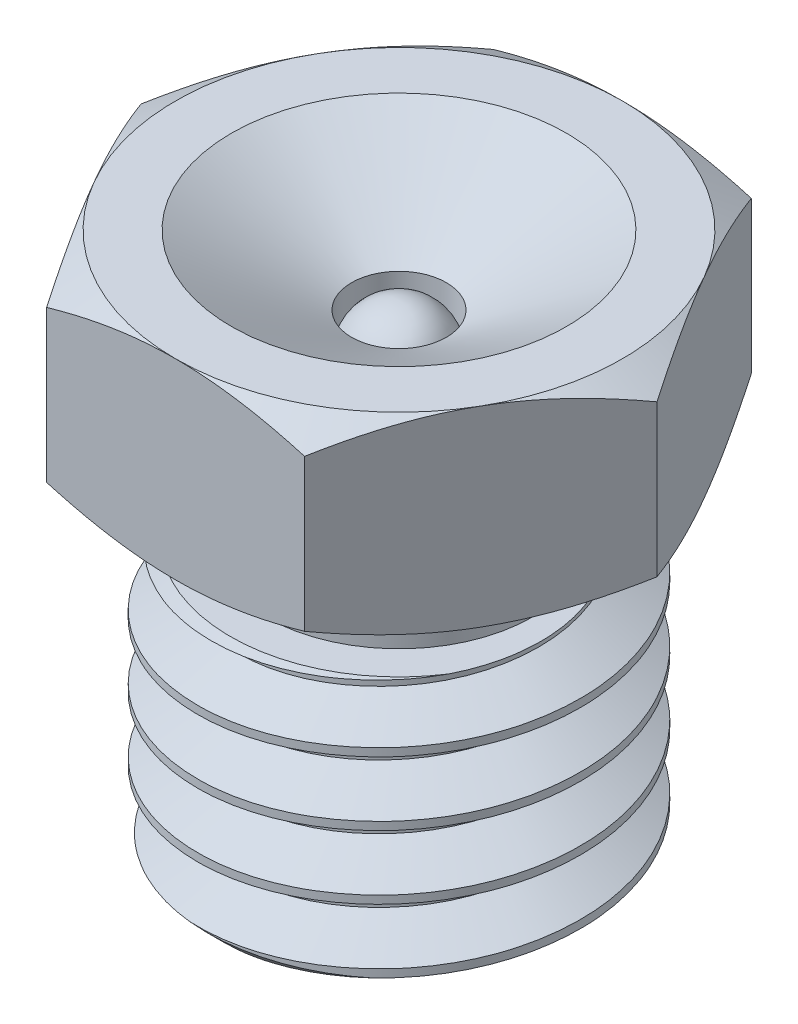
SolidWorks part; units mm, degrees
ref_plane "Front" through (0, 0, 0) normal (0, 0, 1) x (1, 0, 0)
ref_plane "Top" through (0, 0, 0) normal (0, 1, 0) x (1, 0, 0)
ref_plane "Right" through (0, 0, 0) normal (1, 0, 0) x (0, 0, -1)
sketch "Sketch1" plane through (0, 0, 0) normal (0, 0, 1) x (1, 0, 0)
  line L0 (0, 3) -> (0, -6) construction
  point P2 (0, -1.2)
  point P3 (0, 0)
  point P5 (0, -5.4)
  dimension "D1" = 0.6
sketch "Sketch2" plane through (0, 0, 0) normal (0, 0, 1) x (1, 0, 0)
  line L0 (0, 0) -> (0, -6)
  line L1 (0, 0) -> (2.1, 0)
  line L2 (2.1, 0) -> (2.1, -1.2)
  line L3 (2.1, -1.2) -> (3, -1.2)
  line L4 (3, -1.2) -> (3, -5.4)
  line L5 (3, -5.4) -> (1.65, -5.4)
  line L6 (1.65, -5.4) -> (1.65, -6)
  line L7 (1.65, -6) -> (0, -6)
  point P10 (-1.65, -6)
  point P11 (-3, -1.2)
  point P14 (-2.1, 0)
  point P15 (-3, -5.4)
  point P16 (3, -4.4)
  point P17 (-3, -4.4)
  dimension "D3" = 3.3
  dimension "D1" = 6
  dimension "D2" = 0.6
  dimension "D4" = 1
  dimension "D5" = 4.2
revolve "Revolve1" add sketch "Sketch2" angle 360 mid plane about L0
sketch "Sketch3" plane through (0, -5.4, 0) normal (0, -1, 0) x (1, 0, 0)
  circle A0 centre (0, 0) radius 3
chamfer "Chamfer1" distance 0.36 angle 45 2 edges at (-3, -5.4, 0) (-3, -1.2, 0)
curve "Helix/Spiral1" pitch 1 height 5.2 radius 3 centre (0, -5.4, 0) axis (0, 1, 0) start towards (1, 0, 0)
fillet "Fillet1" radius 0.231 2 edges at (-1.65, -6, 0) (-1.65, -5.4, 0)
sketch "Sketch4" plane through (0, 0, 0) normal (0, 0, 1) x (1, 0, 0)
  line L0 (-3, -5.4) -> (-3, -6.275)
  line L1 (-3, -5.4) -> (-2.3505, -5.775)
  line L2 (-2.3505, -5.775) -> (-2.3505, -5.9)
  line L3 (-2.3505, -5.9) -> (-3, -6.275)
  line L6 (-2.6752, -5.5875) -> (-2.6752, -6.0875) construction
  dimension "D1" = 60
  dimension "D3" = 0.125
  dimension "D4" = 0.5
sweep "Cut-Sweep1" cut profiles "Sketch4" path "Helix/Spiral1" align with end faces yes
sketch "Sketch5" plane through (0, 0, 0) normal (0, 1, 0) x (1, 0, 0)
  line L1 (4.0415, 0) -> (2.0207, 3.5)
  line L2 (2.0207, 3.5) -> (-2.0207, 3.5)
  line L3 (-2.0207, 3.5) -> (-4.0415, 0)
  line L4 (-4.0415, 0) -> (-2.0207, -3.5)
  line L5 (-2.0207, -3.5) -> (2.0207, -3.5)
  line L6 (2.0207, -3.5) -> (4.0415, 0)
  circle A0 centre (0, 0) radius 3.5 construction
extrude "Boss-Extrude1" add sketch "Sketch5" along normal up to vertex (3 mm away) up to point (0, 3, 0)
sketch "Sketch6" plane through (0, 0, 0) normal (0, -1, 0) x (1, 0, 0)
  line L0 (-4.0415, 0) -> (-2.0207, 3.5) construction
  circle A0 centre (0, 0) radius 3.5
extrude "Cut-Extrude1" cut sketch "Sketch6" against normal blind 2.54 draft 60 flip side to cut
sketch "Sketch7" plane through (0, 3, 0) normal (0, 1, 0) x (1, 0, 0)
  circle A0 centre (0, 0) radius 3.5 construction
  circle A1 centre (0, 0) radius 3.5
extrude "Cut-Extrude2" cut sketch "Sketch7" against normal blind 2.54 draft 60 flip side to cut
sketch "Sketch11" plane through (0, 0, 0) normal (0, -1, 0) x (1, 0, 0)
  circle A0 centre (0, 0) radius 2.1 construction
  circle A1 centre (0, 0) radius 2.1
extrude "Boss-Extrude2" add sketch "Sketch11" along normal up to vertex (1.2 mm away) up to point (2.1, -1.2, 0)
sketch "Sketch8" plane through (0, 3, 0) normal (0, 1, 0) x (1, 0, 0)
  circle A0 centre (0, 0) radius 2.625
  dimension "D1" = 5.25
extrude "Cut-Extrude3" cut sketch "Sketch8" against normal through all draft 60
sketch "Sketch9" plane through (0, -6, 0) normal (0, -1, 0) x (1, 0, 0)
  circle A0 centre (0, 0) radius 0.7425
  dimension "D1" = 1.485
extrude "Cut-Extrude4" cut sketch "Sketch9" against normal through all
sketch "Sketch10" plane through (0, 0, 0) normal (0, 0, 1) x (1, 0, 0)
  line L0 (0, 3) -> (0, -6) construction
  line L1 (-0.7425, 1.9131) -> (-0.7425, -6) construction
  line L2 (-0.7425, 1.9131) -> (0.7425, 1.9131) construction
  line L3 (0, 2.0401) -> (0, 0.5551)
  arc A0 (0, 0.5551) -> (0, 2.0401) centre (0, 1.2976) ccw
  dimension "D1" = 0.127
revolve "Revolve2" add sketch "Sketch10" angle 360 mid plane about L0
equation "\"C Thread Lg.@Sketch1\" = \"B Shank Lg.@Sketch1\"*.8"
equation "\"D1@Sketch1\" = \"C Thread Lg.@Sketch1\"*.125"
equation "\"D3@Sketch2\" = \"D1@Sketch2\"*.55"
equation "\"D1@Chamfer1\" = \"D Thread OD@Sketch2\"*.06"
equation "\"D3@Helix/Spiral1\" = \"D4@Helix/Spiral1\"+(\"C Thread Lg.@Sketch1\"-\"D1@Sketch1\")"
equation "\"D1@Fillet1\" = \"D3@Sketch2\"*.07"
equation "\"D3@Sketch4\" = \"D4@Helix/Spiral1\"*.125"
equation "\"D4@Sketch4\" = \"D4@Helix/Spiral1\"*.5"
equation "\"D4@Sketch2\" = \"D4@Helix/Spiral1\""
equation "\"D5@Sketch2\" = \"D Thread OD@Sketch2\"*.7"
equation "\"D1@Sketch8\" = \"G Hex Size@Sketch5\"*.75"
equation "\"D1@Sketch9\" = \"D3@Sketch2\"*.45"
